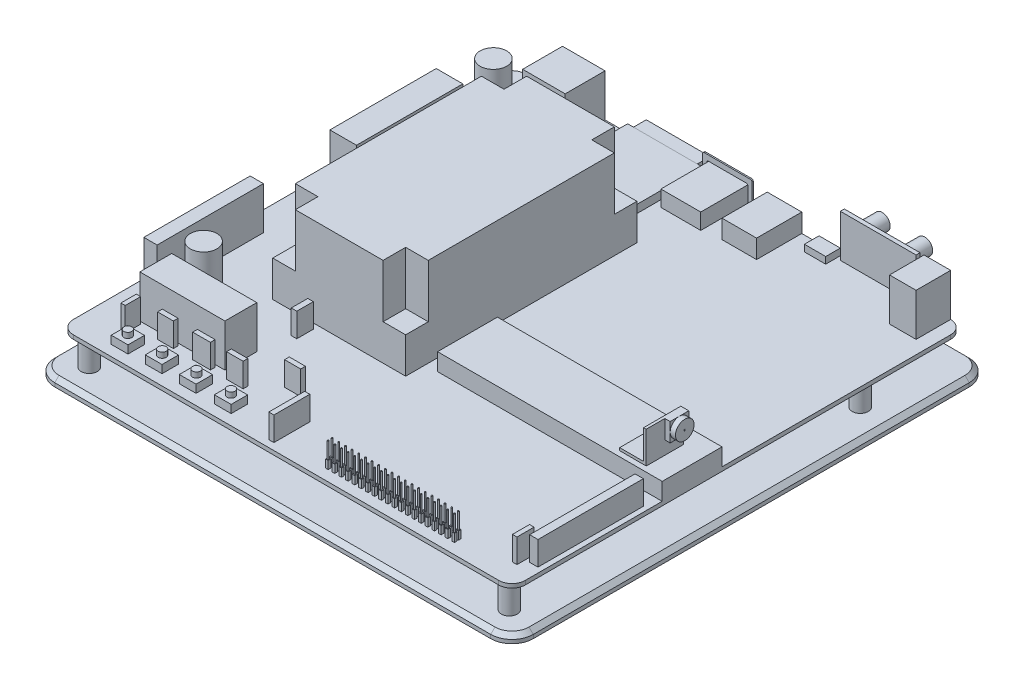
SolidWorks part; units mm, degrees
ref_plane "Plano frontal" through (0, 0, 0) normal (0, 0, 1) x (1, 0, 0)
ref_plane "Plano superior" through (0, 0, 0) normal (0, 1, 0) x (1, 0, 0)
ref_plane "Plano direito" through (0, 0, 0) normal (1, 0, 0) x (0, 0, -1)
sketch "Esboço1" plane through (0, 0, 0) normal (0, 1, 0) x (1, 0, 0)
  line L1 (82, -90) -> (-82, -90)
  line L2 (90, -82) -> (90, 82)
  line L3 (82, 90) -> (-82, 90)
  line L4 (-90, -82) -> (-90, 82)
  line L5 (90, -90) -> (-90, 90) construction
  line L6 (90, 90) -> (-90, -90) construction
  arc A0 (82, -90) -> (90, -82) centre (82, -82) ccw
  arc A1 (-82, -90) -> (-90, -82) centre (-82, -82) cw
  arc A2 (90, 82) -> (82, 90) centre (82, 82) ccw
  arc A3 (-82, 90) -> (-90, 82) centre (-82, 82) ccw
  point P0 (0, 0)
  dimension "D3" = 8
  dimension "D1" = 180
  dimension "D2" = 180
extrude "Ressalto-extrusão1" add sketch "Esboço1" along normal blind 3
sketch "Esboço2" plane through (0, 0, 0) normal (0, -1, 0) x (-1, 0, 0)
  line L0 (82, -90) -> (-82, -90) construction
  line L1 (90, 82) -> (90, -82) construction
  line L2 (0, 0) -> (-90, 0) construction
  line L3 (-90, -82) -> (-90, 82) construction
  line L4 (0, 0) -> (0, -90) construction
  circle A0 centre (79, -62) radius 3.5
  circle A1 centre (-79, -62) radius 3.5
  circle A2 centre (-79, 62) radius 3.5
  circle A3 centre (79, 62) radius 3.5
  dimension "D1" = 7
  dimension "D2" = 28
  dimension "D3" = 11
extrude "Ressalto-extrusão2" add sketch "Esboço2" along normal blind 5
sketch "Esboço3" plane through (0, 3, 0) normal (0, 1, 0) x (1, 0, 0)
  line L0 (90, -82) -> (90, 82) construction
  line L1 (-82, -90) -> (82, -90) construction
  line L2 (-90, 82) -> (-90, -82) construction
  line L3 (82, 90) -> (-82, 90) construction
  circle A0 centre (-79, -80) radius 3
  circle A1 centre (-79, 75) radius 3
  circle A2 centre (79, 52) radius 3
  circle A3 centre (79, -80) radius 3
  dimension "D1" = 6
  dimension "D3" = 11
  dimension "D5" = 10
  dimension "D6" = 38
  dimension "D2" = 10
  dimension "D4" = 11
  dimension "D7" = 15
extrude "Ressalto-extrusão3" add sketch "Esboço3" along normal blind 11
sketch "Esboço4" plane through (0, 14, 0) normal (0, 1, 0) x (1, 0, 0)
  line L1 (-80, 85) -> (80, 85)
  line L2 (-85, 80) -> (-85, -80)
  line L3 (-80, -85) -> (80, -85)
  line L4 (85, 80) -> (85, -80)
  line L5 (-85, 85) -> (85, -85) construction
  line L6 (-85, -85) -> (85, 85) construction
  arc A1 (80, -85) -> (85, -80) centre (80, -80) ccw
  arc A2 (-85, -80) -> (-80, -85) centre (-80, -80) ccw
  arc A3 (80, 85) -> (85, 80) centre (80, 80) cw
  arc A4 (-80, 85) -> (-85, 80) centre (-80, 80) ccw
  point P0 (0, 0)
  dimension "D3" = 5
  dimension "D1" = 170
  dimension "D2" = 170
extrude "Ressalto-extrusão4" add sketch "Esboço4" along normal blind 1.5
sketch "Esboço5" plane through (0, 15.5, 0) normal (0, 1, 0) x (1, 0, 0)
  line L0 (-80, -85) -> (80, -85) construction
  line L1 (-54, 51) -> (-4, 51)
  line L2 (-54, 51) -> (-54, -36)
  line L3 (-54, -36) -> (-4, -36)
  line L4 (-4, 51) -> (-4, -36)
  line L5 (-54, 51) -> (-4, -36) construction
  line L6 (-54, -36) -> (-4, 51) construction
  line L7 (-85, 80) -> (-85, -80) construction
  point P0 (-29, 7.5)
  dimension "D1" = 50
  dimension "D2" = 87
  dimension "D3" = 49
  dimension "D4" = 31
extrude "Ressalto-extrusão5" add sketch "Esboço5" along normal blind 33.5
sketch "Esboço6" plane through (0, 49, 0) normal (0, 1, 0) x (1, 0, 0)
  line L0 (-54, 7.5) -> (-4, 7.5) construction
  line L1 (-54, -36) -> (-45.5, -36)
  line L2 (-54, -36) -> (-54, -27.5)
  line L3 (-54, -27.5) -> (-45.5, -27.5)
  line L4 (-45.5, -36) -> (-45.5, -27.5)
  line L5 (-54, 51) -> (-54, -36) construction
  line L6 (-4, -36) -> (-4, 51) construction
  line L7 (-29, 51) -> (-29, -36) construction
  line L8 (-4, 51) -> (-54, 51) construction
  line L9 (-54, -36) -> (-4, -36) construction
  line L10 (-12.5, -36) -> (-12.5, -27.5)
  line L11 (-4, -36) -> (-12.5, -36)
  line L12 (-4, -36) -> (-4, -27.5)
  line L13 (-4, -27.5) -> (-12.5, -27.5)
  line L14 (-4, 42.5) -> (-12.5, 42.5)
  line L15 (-4, 51) -> (-4, 42.5)
  line L16 (-4, 51) -> (-12.5, 51)
  line L17 (-12.5, 51) -> (-12.5, 42.5)
  line L18 (-45.5, 51) -> (-45.5, 42.5)
  line L19 (-54, 42.5) -> (-45.5, 42.5)
  line L20 (-54, 51) -> (-54, 42.5)
  line L21 (-54, 51) -> (-45.5, 51)
  dimension "D1" = 8.5
  dimension "D2" = 8.5
extrude "Corte-extrusão1" cut sketch "Esboço6" against normal blind 20
sketch "Esboço7" plane through (0, 15.5, 0) normal (0, 1, 0) x (1, 0, 0)
  line L0 (-30.95, -74.8) -> (-24.65, -74.8)
  line L1 (-69.75, -74.8) -> (-63.45, -74.8)
  line L2 (-69.75, -74.8) -> (-69.75, -81)
  line L3 (-69.75, -81) -> (-63.45, -81)
  line L4 (-63.45, -74.8) -> (-63.45, -81)
  line L5 (-69.75, -74.8) -> (-63.45, -81) construction
  line L6 (-69.75, -81) -> (-63.45, -74.8) construction
  line L7 (-80, -85) -> (80, -85) construction
  line L8 (-85, 80) -> (-85, -80) construction
  line L9 (-56.95, -74.8) -> (-50.65, -74.8)
  line L10 (-56.95, -74.8) -> (-56.95, -81)
  line L11 (-56.95, -81) -> (-50.65, -81)
  line L12 (-50.65, -74.8) -> (-50.65, -81)
  line L13 (-56.95, -74.8) -> (-50.65, -81) construction
  line L14 (-56.95, -81) -> (-50.65, -74.8) construction
  line L15 (-44.15, -74.8) -> (-37.85, -74.8)
  line L16 (-44.15, -74.8) -> (-44.15, -81)
  line L17 (-44.15, -81) -> (-37.85, -81)
  line L18 (-37.85, -74.8) -> (-37.85, -81)
  line L19 (-44.15, -74.8) -> (-37.85, -81) construction
  line L20 (-44.15, -81) -> (-37.85, -74.8) construction
  line L21 (-30.95, -74.8) -> (-30.95, -81)
  line L22 (-30.95, -81) -> (-24.65, -81)
  line L23 (-24.65, -74.8) -> (-24.65, -81)
  line L24 (-30.95, -74.8) -> (-24.65, -81) construction
  line L25 (-30.95, -81) -> (-24.65, -74.8) construction
  point P0 (-66.6, -77.9)
  point P10 (-27.8, -77.9)
  point P11 (-53.8, -77.9)
  point P16 (-41, -77.9)
  dimension "D1" = 6.2
  dimension "D2" = 6.3
  dimension "D3" = 4
  dimension "D4" = 15.25
  dimension "D5" = 3
  dimension "D6" = 6.5
  dimension "D8" = 6.9
  dimension "D7" = 2
extrude "Ressalto-extrusão6" add sketch "Esboço7" along normal blind 3
sketch "Esboço8" plane through (0, 18.5, 0) normal (0, 1, 0) x (1, 0, 0)
  line L0 (-63.45, -81) -> (-63.45, -74.8) construction
  line L2 (-69.75, -81) -> (-63.45, -81) construction
  line L3 (-24.65, -81) -> (-24.65, -74.8) construction
  line L4 (-24.65, -74.8) -> (-30.95, -74.8) construction
  circle A0 centre (-66.6, -77.9) radius 1.5
  circle A1 centre (-53.7, -77.9) radius 1.5
  circle A2 centre (-40.8, -77.9) radius 1.5
  circle A3 centre (-27.75, -77.95) radius 1.5
  point P6 (-66.6, -81)
  dimension "D1" = 3.15
  dimension "D2" = 3.1
  dimension "D3" = 3
  dimension "D5" = 3
  dimension "D6" = 3.1
  dimension "D7" = 3.15
  dimension "D8" = 12.9
  dimension "D4" = 3
extrude "Ressalto-extrusão7" add sketch "Esboço8" along normal blind 2
sketch "Esboço9" plane through (0, 15.5, 0) normal (0, 1, 0) x (1, 0, 0)
  line L0 (-80, -85) -> (80, -85) construction
  line L1 (10.85, -80) -> (11.85, -80)
  line L2 (10.85, -80) -> (10.85, -81)
  line L3 (10.85, -81) -> (11.85, -81)
  line L4 (11.85, -80) -> (11.85, -81)
  line L5 (10.85, -80) -> (11.85, -81) construction
  line L6 (10.85, -81) -> (11.85, -80) construction
  line L7 (-24.65, -81) -> (-24.65, -74.8) construction
  point P0 (11.35, -80.5)
  dimension "D1" = 1
  dimension "D2" = 4
  dimension "D3" = 35.5
extrude "Ressalto-extrusão8" add sketch "Esboço9" along normal blind 3
sketch "Esboço10" plane through (0, 18.5, 0) normal (0, 1, 0) x (1, 0, 0)
  line L1 (11.35, -80) -> (11.35, -80.5) construction
  line L2 (11.85, -80) -> (10.85, -80) construction
  line L3 (11.35, -80.5) -> (11.85, -80.5) construction
  line L4 (11.85, -81) -> (11.85, -80) construction
  circle A0 centre (11.35, -80.5) radius 0.25
  dimension "D1" = 0.5
extrude "Ressalto-extrusão9" add sketch "Esboço10" along normal blind 6
pattern_linear "Padrão linear1" count 20 spacing 2.5 along (1, 0, 0) count 2 spacing 1.5 along (0, 0, -1) of "Ressalto-extrusão8", "Ressalto-extrusão9"
sketch "Esboço11" plane through (0, 15.5, 0) normal (0, 1, 0) x (1, 0, 0)
  line L0 (80, 85) -> (-80, 85) construction
  line L1 (-71.9966, -56) -> (-39.9966, -56)
  line L2 (-71.9966, -56) -> (-71.9966, -68)
  line L3 (-71.9966, -68) -> (-39.9966, -68)
  line L4 (-39.9966, -56) -> (-39.9966, -68)
  line L5 (-82.5, -56) -> (-77.5, -56)
  line L6 (-82.5, -56) -> (-82.5, -16)
  line L7 (-82.5, -16) -> (-77.5, -16)
  line L8 (-77.5, -56) -> (-77.5, -16)
  line L9 (-82.5, 54) -> (-72.5, 54)
  line L10 (-82.5, 54) -> (-82.5, 14)
  line L11 (-82.5, 14) -> (-72.5, 14)
  line L12 (-72.5, 54) -> (-72.5, 14)
  line L13 (-66, 85) -> (-50, 85)
  line L14 (-66, 85) -> (-66, 70)
  line L15 (-66, 70) -> (-50, 70)
  line L16 (-50, 85) -> (-50, 70)
  line L17 (-85, 80) -> (-85, -80) construction
  line L18 (-80, -85) -> (80, -85) construction
  line L19 (80, 85) -> (70, 85)
  line L20 (80, 85) -> (80, 72)
  line L21 (80, 72) -> (70, 72)
  line L22 (70, 85) -> (70, 72)
  line L23 (68.5, 85) -> (40, 85)
  line L24 (68.5, 85) -> (68.5, 83.5)
  line L25 (68.5, 83.5) -> (40, 83.5)
  line L26 (40, 85) -> (40, 83.5)
  circle A0 centre (-70, -46) radius 5
  circle A1 centre (-75, 68) radius 5
  dimension "D1" = 10
  dimension "D2" = 10
  dimension "D12" = 17
  dimension "D26" = 10
  dimension "D3" = 15
  dimension "D4" = 16
  dimension "D5" = 19
  dimension "D6" = 13
  dimension "D7" = 10
  dimension "D8" = 28.5
  dimension "D9" = 1.5
  dimension "D10" = 1.5
  dimension "D11" = 10
  dimension "D13" = 10
  dimension "D14" = 40
  dimension "D15" = 2.5
  dimension "D16" = 2.5
  dimension "D17" = 5
  dimension "D18" = 29
  dimension "D19" = 30
  dimension "D20" = 40
  dimension "D21" = 7.5
  dimension "D22" = 12
  dimension "D23" = 32
  dimension "D24" = 13.0034
  dimension "D25" = 17
extrude "Ressalto-extrusão10" add sketch "Esboço11" along normal blind 16
sketch "Esboço12" plane through (0, 0, -85) normal (0, 0, -1) x (-1, 0, 0)
  line L0 (-68.5, 31.5) -> (-40, 31.5) construction
  line L1 (-62.25, 26.5) -> (-68.5, 26.5) construction
  line L2 (-68.5, 31.5) -> (-68.5, 15.5) construction
  line L3 (-46.25, 26.5) -> (-40, 26.5) construction
  line L4 (-40, 31.5) -> (-40, 15.5) construction
  circle A0 centre (-62.25, 26.5) radius 3
  circle A1 centre (-46.25, 26.5) radius 3
  dimension "D1" = 6
  dimension "D2" = 6
  dimension "D3" = 5
  dimension "D4" = 16
extrude "Ressalto-extrusão11" add sketch "Esboço12" along normal blind 8
sketch "Esboço13" plane through (0, 15.5, 0) normal (0, 1, 0) x (1, 0, 0)
  line L0 (-69.75, -74.8) -> (-69.75, -81) construction
  line L1 (-70.7943, -68.907) -> (-72.4259, -68.907)
  line L2 (-70.7943, -68.907) -> (-70.7943, -74.6918)
  line L3 (-70.7943, -74.6918) -> (-72.4259, -74.6918)
  line L4 (-72.4259, -68.907) -> (-72.4259, -74.6918)
  line L5 (-62.6363, -68.907) -> (-56.7033, -68.907)
  line L6 (-62.6363, -68.907) -> (-62.6363, -70.6869)
  line L7 (-62.6363, -70.6869) -> (-56.7033, -70.6869)
  line L8 (-56.7033, -68.907) -> (-56.7033, -70.6869)
  line L9 (-49.4353, -68.907) -> (-42.7606, -68.907)
  line L10 (-49.4353, -68.907) -> (-49.4353, -70.6869)
  line L11 (-49.4353, -70.6869) -> (-42.7606, -70.6869)
  line L12 (-42.7606, -68.907) -> (-42.7606, -70.6869)
  line L13 (-36.6792, -68.907) -> (-30.4495, -68.907)
  line L14 (-36.6792, -68.907) -> (-36.6792, -70.6869)
  line L15 (-36.6792, -70.6869) -> (-30.4495, -70.6869)
  line L16 (-30.4495, -68.907) -> (-30.4495, -70.6869)
  line L17 (-9.0905, -68.907) -> (-7.1623, -68.907)
  line L18 (-9.0905, -68.907) -> (-9.0905, -82.4047)
  line L19 (-9.0905, -82.4047) -> (-7.1623, -82.4047)
  line L20 (-7.1623, -68.907) -> (-7.1623, -82.4047)
  line L21 (-23.1815, -60.6008) -> (-17.1002, -60.6008)
  line L22 (-23.1815, -60.6008) -> (-23.1815, -62.3807)
  line L23 (-23.1815, -62.3807) -> (-17.1002, -62.3807)
  line L24 (-17.1002, -60.6008) -> (-17.1002, -62.3807)
  line L25 (-38.7558, -38.0552) -> (-36.6792, -38.0552)
  line L26 (-38.7558, -38.0552) -> (-38.7558, -44.2849)
  line L27 (-38.7558, -44.2849) -> (-36.6792, -44.2849)
  line L28 (-36.6792, -38.0552) -> (-36.6792, -44.2849)
  line L29 (83.0751, -73.3111) -> (79.9494, -73.3111)
  line L30 (83.0751, -73.3111) -> (83.0751, -33.6552)
  line L31 (83.0751, -33.6552) -> (79.9494, -33.6552)
  line L32 (79.9494, -73.3111) -> (79.9494, -33.6552)
  line L33 (78.3022, -70.0067) -> (76.6024, -70.0067)
  line L34 (78.3022, -70.0067) -> (78.3022, -76.444)
  line L35 (78.3022, -76.444) -> (76.6024, -76.444)
  line L36 (76.6024, -70.0067) -> (76.6024, -76.444)
  line L37 (-63.45, -74.8) -> (-69.75, -74.8) construction
  dimension "D1" = 7.1137
  dimension "D2" = 13.0467
  dimension "D3" = 20.3147
  dimension "D4" = 26.9894
  dimension "D5" = 30.9942
  dimension "D6" = 33.0708
  dimension "D7" = 39.3005
  dimension "D8" = 46.5685
  dimension "D9" = 52.6498
  dimension "D10" = 60.6595
  dimension "D11" = 62.5877
  dimension "D12" = 146.3524
  dimension "D13" = 148.0522
  dimension "D14" = 149.6994
  dimension "D15" = 152.8251
  dimension "D16" = 1.0443
  dimension "D17" = 2.6759
  dimension "D18" = 0.1082
  dimension "D19" = 1.4889
  dimension "D20" = 4.1131
  dimension "D21" = 4.7933
  dimension "D22" = 5.893
  dimension "D23" = 12.4193
  dimension "D24" = 30.5151
  dimension "D27" = 41.1448
  dimension "D28" = 1.644
  dimension "D29" = 7.6047
extrude "Ressalto-extrusão12" add sketch "Esboço13" along normal blind 9
sketch "Esboço14" plane through (0, 15.5, 0) normal (0, 1, 0) x (1, 0, 0)
  line L0 (85, -80) -> (85, 80) construction
  line L1 (85, -28.5) -> (0.5, -28.5)
  line L2 (85, -28.5) -> (85, -6)
  line L3 (85, -6) -> (0.5, -6)
  line L4 (0.5, -28.5) -> (0.5, -6)
  line L5 (-80, -85) -> (80, -85) construction
  dimension "D1" = 56.5
  dimension "D2" = 84.5
  dimension "D3" = 22.5
extrude "Ressalto-extrusão13" add sketch "Esboço14" along normal blind 6.5
sketch "Esboço15" plane through (0, 22, 0) normal (0, 1, 0) x (1, 0, 0)
  line L0 (85, -28.5) -> (85, -6) construction
  line L1 (77, -12.5) -> (76, -12.5)
  line L2 (77, -12.5) -> (77, -26.5)
  line L3 (77, -26.5) -> (76, -26.5)
  line L4 (76, -12.5) -> (76, -26.5)
  line L5 (0.5, -28.5) -> (85, -28.5) construction
  dimension "D1" = 14
  dimension "D2" = 1
  dimension "D3" = 8
  dimension "D4" = 2
extrude "Ressalto-extrusão14" add sketch "Esboço15" along normal blind 12
sketch "Esboço16" plane through (76, 0, 0) normal (-1, 0, 0) x (0, 0, 1)
  line L0 (26.5, 34) -> (26.5, 22) construction
  line L1 (12.5, 22) -> (26.5, 22)
  line L2 (12.5, 22) -> (12.5, 23)
  line L3 (12.5, 23) -> (26.5, 23)
  line L4 (26.5, 22) -> (26.5, 23)
  dimension "D1" = 1
extrude "Ressalto-extrusão15" add sketch "Esboço16" along normal blind 9
sketch "Esboço17" plane through (77, 0, 0) normal (1, 0, 0) x (0, 0, -1)
  line L1 (-12.5, 34) -> (-19.5, 34)
  line L2 (-12.5, 34) -> (-12.5, 27)
  line L3 (-12.5, 27) -> (-19.5, 27)
  line L4 (-19.5, 34) -> (-19.5, 27)
  dimension "D1" = 7
  dimension "D2" = 7
extrude "Ressalto-extrusão16" add sketch "Esboço17" along normal blind 2
sketch "Esboço18" plane through (79, 0, 0) normal (1, 0, 0) x (0, 0, -1)
  line L0 (-16, 34) -> (-16, 30.5) construction
  line L1 (-12.5, 34) -> (-19.5, 34) construction
  line L2 (-16, 30.5) -> (-12.5, 30.5) construction
  line L3 (-12.5, 27) -> (-12.5, 34) construction
  circle A0 centre (-16, 30.5) radius 3.5
  dimension "D1" = 7
extrude "Ressalto-extrusão17" add sketch "Esboço18" along normal blind 2
sketch "Esboço19" plane through (81, 0, 0) normal (1, 0, 0) x (0, 0, -1)
  circle A0 centre (-16, 30.5) radius 0.35
  circle A1 centre (-16, 30.5) radius 0.25
  dimension "D1" = 0.5
  dimension "D2" = 0.1
extrude "Corte-extrusão2" cut sketch "Esboço19" against normal blind 0.2
sketch "Esboço20" plane through (0, 15.5, 0) normal (0, 1, 0) x (1, 0, 0)
  line L0 (40, 85) -> (-50, 85) construction
  line L1 (-41.5, 85) -> (-13.5, 85)
  line L2 (-41.5, 85) -> (-41.5, 56)
  line L3 (-41.5, 56) -> (-13.5, 56)
  line L4 (-13.5, 85) -> (-13.5, 56)
  line L5 (-50, 70) -> (-50, 85) construction
  line L6 (-39.5, 85) -> (-15.5, 85)
  line L7 (-39.5, 85) -> (-39.5, 90)
  line L8 (-39.5, 90) -> (-15.5, 90)
  line L9 (-15.5, 85) -> (-15.5, 90)
  point P12 (-27.5, 90)
  point P13 (-27.5, 85)
  dimension "D1" = 8.5
  dimension "D2" = 28
  dimension "D3" = 29
  dimension "D4" = 5
  dimension "D5" = 24
extrude "Ressalto-extrusão18" add sketch "Esboço20" along normal blind 3 contours L1 L9 L8 L7 | L4 L1 L2 L3 region at (-27.5, 15.5, -70.5) region at (-27.5, 15.5, -87.5)
sketch "Esboço21" plane through (0, 0, -90) normal (0, 0, -1) x (-1, 0, 0)
  line L0 (15.5, 18.5) -> (15.5, 15.5) construction
  line L1 (39.5, 15.5) -> (15.5, 15.5)
  line L2 (39.5, 15.5) -> (39.5, 15.7)
  line L3 (39.5, 15.7) -> (15.5, 15.7)
  line L4 (15.5, 15.5) -> (15.5, 15.7)
  line L5 (39.5, 17) -> (15.5, 17) construction
  line L6 (39.5, 18.5) -> (39.5, 15.5) construction
  line L7 (15.5, 18.5) -> (15.5, 18.3)
  line L8 (39.5, 18.3) -> (15.5, 18.3)
  line L9 (39.5, 18.5) -> (39.5, 18.3)
  line L10 (39.5, 18.5) -> (15.5, 18.5)
  dimension "D1" = 0.2
extrude "Corte-extrusão3" cut sketch "Esboço21" against normal blind 5
sketch "Esboço22" plane through (0, 15.5, 0) normal (0, 1, 0) x (1, 0, 0)
  line L0 (40, 85) -> (-13.5, 85) construction
  line L1 (-11, 85) -> (4, 85)
  line L2 (-11, 85) -> (-11, 67)
  line L3 (-11, 67) -> (4, 67)
  line L4 (4, 85) -> (4, 67)
  line L5 (-13.5, 85) -> (-13.5, 56) construction
  dimension "D1" = 15
  dimension "D2" = 18
  dimension "D3" = 2.5
extrude "Ressalto-extrusão19" add sketch "Esboço22" along normal blind 6
sketch "Esboço23" plane through (0, 15.5, 0) normal (0, 1, 0) x (1, 0, 0)
  line L0 (40, 85) -> (4, 85) construction
  line L1 (11, 85) -> (24, 85)
  line L2 (11, 85) -> (11, 68)
  line L3 (11, 68) -> (24, 68)
  line L4 (24, 85) -> (24, 68)
  line L5 (4, 67) -> (4, 85) construction
  dimension "D1" = 13
  dimension "D2" = 17
  dimension "D3" = 7
extrude "Ressalto-extrusão20" add sketch "Esboço23" along normal blind 7
sketch "Esboço24" plane through (0, 15.5, 0) normal (0, 1, 0) x (1, 0, 0)
  line L0 (40, 85) -> (24, 85) construction
  line L1 (30.5, 85) -> (38.5, 85)
  line L2 (30.5, 85) -> (30.5, 79.5)
  line L3 (30.5, 79.5) -> (38.5, 79.5)
  line L4 (38.5, 85) -> (38.5, 79.5)
  line L5 (24, 68) -> (24, 85) construction
  dimension "D1" = 8
  dimension "D2" = 5.5
  dimension "D3" = 6.5
extrude "Ressalto-extrusão21" add sketch "Esboço24" along normal blind 2.5
sketch "Esboço25" plane through (0, 0, -85) normal (0, 0, -1) x (-1, 0, 0)
  line L0 (-3.5, 20) -> (10.5, 20)
  line L1 (10.5, 20) -> (10.5, 17)
  line L2 (10.5, 17) -> (9, 15.5)
  line L3 (9, 15.5) -> (-2, 15.5)
  line L4 (-2, 15.5) -> (-3.5, 17)
  line L5 (-3.5, 17) -> (-3.5, 20)
  line L6 (10.5, 20) -> (11, 20) construction
  line L7 (11, 21.5) -> (11, 15.5) construction
  line L8 (-3.5, 20) -> (-4, 20) construction
  line L9 (-4, 21.5) -> (-4, 15.5) construction
  line L10 (3.5, 20) -> (3.5, 21.5) construction
  line L11 (-4, 21.5) -> (11, 21.5) construction
  line L12 (3.5, 15.5) -> (3.5, 14) construction
  line L13 (-80, 14) -> (80, 14) construction
  line L14 (-1.5, 17.5) -> (-3.5, 17.5) construction
  line L15 (-1.5, 18) -> (8.5, 18)
  line L16 (-1.5, 18) -> (-1.5, 17.5)
  line L17 (-1.5, 17.5) -> (8.5, 17.5)
  line L18 (8.5, 18) -> (8.5, 17.5)
  line L19 (8.5, 17.5) -> (10.5, 17.5) construction
  point P28 (3.5, 15.5)
  point P29 (3.5, 20)
  dimension "D1" = 14
  dimension "D2" = 3
  dimension "D3" = 4.5
  dimension "D4" = 10
  dimension "D5" = 0.5
  dimension "D6" = 0.5
extrude "Corte-extrusão4" cut sketch "Esboço25" against normal blind 8.5
sketch "Esboço26" plane through (0, 0, -85) normal (0, 0, -1) x (-1, 0, 0)
  line L0 (-4.2, 15.5) -> (-4.2, 21.5)
  line L1 (-85, 15.5) -> (-0.5, 15.5) construction
  line L2 (-3.7, 22) -> (10.7, 22)
  line L3 (11.2, 21.5) -> (11.2, 15.5)
  line L4 (11, 15.5) -> (13.5, 15.5) construction
  line L5 (11.2, 15.5) -> (12.75, 15.5)
  line L6 (4, 15.5) -> (54, 15.5) construction
  line L7 (12.75, 15.5) -> (12.75, 23.5)
  line L8 (12.25, 24) -> (-5.25, 24)
  line L9 (-5.75, 23.5) -> (-5.75, 15.5)
  line L10 (-11, 15.5) -> (-4, 15.5) construction
  line L11 (-5.75, 15.5) -> (-4.2, 15.5)
  line L12 (-4, 21.5) -> (-4, 15.5) construction
  line L13 (11, 21.5) -> (11, 15.5) construction
  line L14 (-4, 21.5) -> (11, 21.5) construction
  arc A0 (10.7, 22) -> (11.2, 21.5) centre (10.7, 21.5) cw
  arc A1 (-4.2, 21.5) -> (-3.7, 22) centre (-3.7, 21.5) cw
  arc A2 (12.75, 23.5) -> (12.25, 24) centre (12.25, 23.5) ccw
  arc A3 (-5.25, 24) -> (-5.75, 23.5) centre (-5.25, 23.5) ccw
  point P28 (12.75, 24)
  point P31 (-5.75, 24)
  dimension "D6" = 0.5
  dimension "D1" = 8.5
  dimension "D2" = 18.5
  dimension "D3" = 0.2
  dimension "D4" = 0.2
  dimension "D5" = 0.5
extrude "Ressalto-extrusão22" add sketch "Esboço26" against normal blind 0.5
sketch "Esboço27" plane through (0, 0, -85) normal (0, 0, -1) x (-1, 0, 0)
  line L0 (-24, 22.5) -> (-24, 15.5) construction
  line L1 (-23.8, 22.3) -> (-11.2, 22.3)
  line L2 (-23.8, 22.3) -> (-23.8, 15.7)
  line L3 (-23.8, 15.7) -> (-11.2, 15.7)
  line L4 (-11.2, 22.3) -> (-11.2, 15.7)
  line L5 (-11, 22.5) -> (-11, 15.5) construction
  line L6 (-24, 22.5) -> (-11, 22.5) construction
  line L7 (-85, 15.5) -> (-0.5, 15.5) construction
  line L8 (-22.8, 21.3) -> (-12.2, 21.3)
  line L9 (-12.2, 21.3) -> (-12.2, 19.8)
  line L10 (-12.2, 21.3) -> (-12.2, 16.7) construction
  line L11 (-22.8, 21.3) -> (-22.8, 19.8)
  line L12 (-22.8, 19.8) -> (-12.2, 19.8)
  line L13 (-22.8, 21.3) -> (-22.8, 16.7) construction
  line L14 (-22.8, 16.7) -> (-12.2, 16.7) construction
  dimension "D1" = 0.2
  dimension "D2" = 0.2
  dimension "D3" = 0.2
  dimension "D4" = 0.2
  dimension "D6" = 1.5
  dimension "D5" = 1
extrude "Corte-extrusão5" cut sketch "Esboço27" against normal blind 10
sketch "Esboço28" plane through (0, 0, -85) normal (0, 0, -1) x (-1, 0, 0)
  line L0 (-40, 15.5) -> (-38.5, 15.5) construction
  line L1 (-37.3, 17.8) -> (-31.7, 17.8)
  line L2 (-38.3, 16.8) -> (-38.3, 16.7)
  line L3 (-37.3, 15.7) -> (-31.7, 15.7)
  line L4 (-30.7, 16.8) -> (-30.7, 16.7)
  line L5 (-38.5, 18) -> (-30.5, 18) construction
  line L6 (-38.5, 18) -> (-38.5, 15.5) construction
  line L7 (-30.5, 18) -> (-30.5, 15.5) construction
  arc A0 (-31.7, 15.7) -> (-30.7, 16.7) centre (-31.7, 16.7) ccw
  arc A1 (-31.7, 17.8) -> (-30.7, 16.8) centre (-31.7, 16.8) cw
  arc A2 (-38.3, 16.7) -> (-37.3, 15.7) centre (-37.3, 16.7) ccw
  arc A3 (-37.3, 17.8) -> (-38.3, 16.8) centre (-37.3, 16.8) ccw
  dimension "D5" = 1
  dimension "D1" = 0.2
  dimension "D2" = 0.2
  dimension "D3" = 0.2
  dimension "D4" = 0.2
extrude "Corte-extrusão6" cut sketch "Esboço28" against normal blind 4
chamfer "Chanfro1" distance 1.6 angle 45 8 edges at (90, 3, 0) (87.6569, 3, -87.6569) (87.6569, 3, 87.6569) (0, 3, -90) (0, 3, 90) (-87.6569, 3, -87.6569) (-87.6569, 3, 87.6569) (-90, 3, 0)
